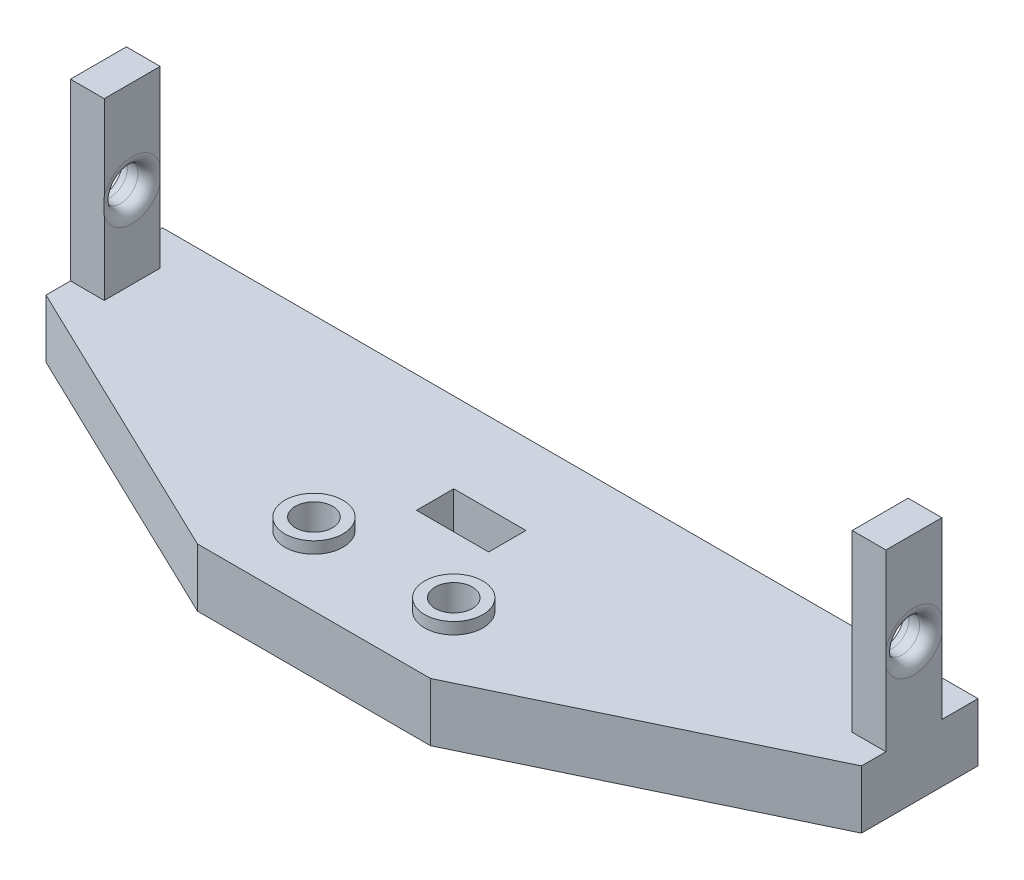
SolidWorks part; units mm, degrees
ref_plane "Front Plane" through (0, 0, 0) normal (0, 0, 1) x (1, 0, 0)
ref_plane "Top Plane" through (0, 0, 0) normal (0, 1, 0) x (1, 0, 0)
ref_plane "Right Plane" through (0, 0, 0) normal (1, 0, 0) x (0, 0, -1)
sketch "Sketch1" plane through (0, 0, 0) normal (0, 1, 0) x (1, 0, 0)
  line L0 (0, 0) -> (20, 0)
  line L1 (10, 0) -> (10, 12) construction
  line L2 (10, 12) -> (-25, 12) construction
  line L3 (0, 0) -> (-25, 12)
  line L4 (-25, 12) -> (-25, 22)
  line L5 (-25, 22) -> (45, 22)
  line L6 (45, 22) -> (45, 12)
  line L7 (45, 12) -> (20, 0)
  dimension "D1" = 35
  dimension "D2" = 20
  dimension "D3" = 12
  dimension "D4" = 70
  dimension "D5" = 10
  dimension "D6" = 10
extrude "Boss-Extrude1" add sketch "Sketch1" along normal blind 5
sketch "Sketch2" plane through (0, 5, 0) normal (0, 1, 0) x (1, 0, 0)
  line L0 (10, 0) -> (10, 22) construction
  line L1 (0, 0) -> (20, 0) construction
  line L2 (45, 22) -> (-25, 22) construction
  circle A0 centre (4, 6) radius 1.6
  circle A1 centre (16, 6) radius 1.6
  dimension "D1" = 3.2
  dimension "D2" = 6
  dimension "D3" = 6
extrude "Cut-Extrude1" cut sketch "Sketch2" against normal blind 3
ref_plane "Plane1" through (0, 0, -6) normal (0, 0, 1) x (1, 0, 0)
sketch "Sketch9" plane through (0, 5, 0) normal (0, 1, 0) x (1, 0, 0)
  line L0 (10, 0) -> (10, 22) construction
  line L1 (0, 0) -> (20, 0) construction
  line L2 (45, 22) -> (-25, 22) construction
  line L3 (10, 11.9) -> (-25, 11.9) construction
  line L4 (-25, 22) -> (-25, 12) construction
  line L5 (-2.75, 6) -> (2.75, 6) construction
  line L7 (6.9, 11.9) -> (13.1, 11.9)
  line L8 (6.9, 11.9) -> (6.9, 15.1)
  line L9 (6.9, 15.1) -> (13.1, 15.1)
  line L10 (13.1, 11.9) -> (13.1, 15.1)
  dimension "D1" = 5.9
  dimension "D2" = 3.1
  dimension "D3" = 3.1
  dimension "D4" = 3.2
sketch "Sketch10" plane through (0, 5, 0) normal (0, 1, 0) x (1, 0, 0)
  line L0 (-25, 22) -> (-25, 12) construction
  line L1 (-25, 18.9) -> (-22.1, 18.9)
  line L2 (-25, 18.9) -> (-25, 14.1)
  line L3 (-25, 14.1) -> (-22.1, 14.1)
  line L4 (-22.1, 18.9) -> (-22.1, 14.1)
  line L5 (45, 22) -> (-25, 22) construction
  line L6 (10, 22) -> (10, 0) construction
  line L7 (0, 0) -> (20, 0) construction
  line L8 (45, 14.1) -> (42.1, 14.1)
  line L9 (42.1, 18.9) -> (42.1, 14.1)
  line L10 (45, 18.9) -> (42.1, 18.9)
  line L11 (45, 18.9) -> (45, 14.1)
  dimension "D1" = 3.1
  dimension "D2" = 4.8
  dimension "D3" = 2.9
extrude "Boss-Extrude2" add sketch "Sketch10" along normal blind 15
extrude "Cut-Extrude4" cut sketch "Sketch9" against normal blind 5
sketch "Sketch11" plane through (-25, 0, 0) normal (-1, 0, 0) x (0, 0, 1)
  circle A0 centre (-16.5, 12) radius 1.5
  dimension "D1" = 3
  dimension "D2" = 7
extrude "Cut-Extrude5" cut sketch "Sketch11" against normal blind 70
fillet "Fillet3" radius 1 1 edges at (-25, 12, -15)
fillet "Fillet4" radius 1 1 edges at (-22.1, 12, -15)
fillet "Fillet6" radius 1 1 edges at (42.1, 12, -18)
fillet "Fillet7" radius 1 1 edges at (45, 12, -15)
sketch "Sketch13" plane through (0, 5, 0) normal (0, 1, 0) x (1, 0, 0)
  line L0 (-12, 22) -> (-17, 29)
  line L1 (45, 22) -> (-25, 22) construction
  line L2 (-17, 29) -> (5, 29)
  line L3 (5, 29) -> (0, 22)
  line L4 (10, 22) -> (10, 29) construction
  line L5 (15, 29) -> (20, 22)
  line L6 (37, 29) -> (15, 29)
  line L7 (32, 22) -> (37, 29)
  line L8 (-12, 22) -> (0, 22)
  line L9 (20, 22) -> (32, 22)
  dimension "D1" = 5
  dimension "D2" = 8
  dimension "D3" = 12
  dimension "D4" = 5
  dimension "D5" = 7
extrude "Boss-Extrude4" [suppressed] add sketch "Sketch13" against normal blind 5
sketch "Sketch14" plane through (0, 5, 0) normal (0, 1, 0) x (1, 0, 0)
  circle A0 centre (4, 6) radius 2.5
  circle A1 centre (16, 6) radius 2.5
  circle A2 centre (16, 6) radius 1.6
  circle A3 centre (4, 6) radius 1.6
  dimension "D1" = 5
  dimension "D2" = 5
extrude "Boss-Extrude5" add sketch "Sketch14" along normal blind 1
